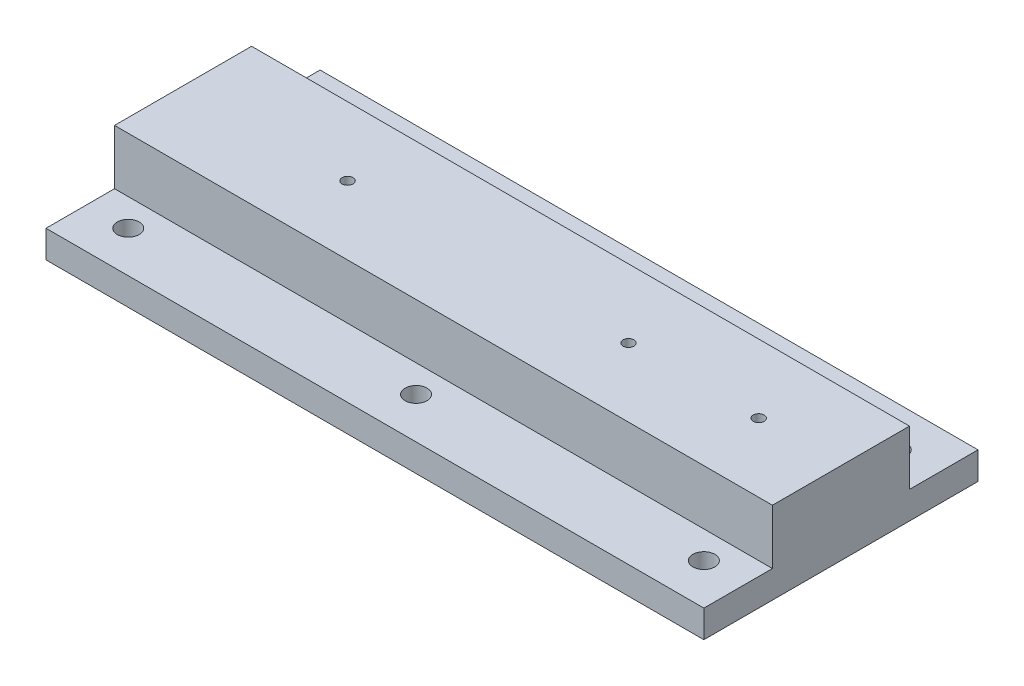
SolidWorks part; units mm, degrees
note: The reader was unsure of these and kept them because the rebuilt part matched: shared geometry of "Skizze7<2>".
ref_plane "Front Plane" through (0, 0, 0) normal (0, 0, 1) x (1, 0, 0)
ref_plane "Top Plane" through (0, 0, 0) normal (0, 1, 0) x (1, 0, 0)
ref_plane "Right Plane" through (0, 0, 0) normal (1, 0, 0) x (0, 0, -1)
sketch "Sketch2" plane through (0, 0, 0) normal (0, 1, 0) x (1, 0, 0)
  line L0 (-46.8981, 34.5466) -> (-46.8981, -15.4534)
  line L1 (-46.8981, -15.4534) -> (73.1019, -15.4534)
  line L2 (73.1019, -15.4534) -> (73.1019, 34.5466)
  line L3 (73.1019, 34.5466) -> (-46.8981, 34.5466)
  dimension "D1" = 120
  dimension "D2" = 50
extrude "Boss-Extrude1" add sketch "Sketch2" along normal blind 15
sketch "Sketch3" plane through (0, 0, 0) normal (0, 1, 0) x (1, 0, 0)
  line L0 (74.3548, 9.5466) -> (-56.2815, 9.5466) construction
  line L1 (63.1019, 9.5466) -> (63.1019, 17.0466)
  line L2 (63.1019, 17.0466) -> (3.1019, 17.0466)
  line L3 (3.1019, 17.0466) -> (3.1019, 19.5466)
  line L4 (3.1019, 19.5466) -> (-36.8981, 19.5466)
  line L5 (-36.8981, 19.5466) -> (-36.8981, 9.5466)
  line L6 (-36.8981, 9.5466) -> (63.1019, 9.5466)
  line L7 (73.1019, -15.4534) -> (73.1019, 34.5466) construction
  line L9 (-46.8981, -15.4534) -> (73.1019, -15.4534) construction
  dimension "D1" = 60
  dimension "D2" = 40
  dimension "D3" = 10
  dimension "D4" = 25
  dimension "D5" = 10
  dimension "D6" = 7.5
revolve "Cut-Revolve8" cut sketch "Sketch3" angle 360 about L0
ref_plane "Ebene1" through (63.1019, 0, 0) normal (-1, 0, 0) x (0, 0, 1)
sketch "Skizze2" plane through (63.1019, 0, 0) normal (-1, 0, 0) x (0, 0, 1)
  line L0 (-22.101, 0) -> (5.7524, 0) construction
  line L1 (-2.0466, 0) -> (-17.0466, 0) construction
  line L2 (-9.5466, -15.2765) -> (-9.5466, 13.7911) construction
  line L3 (-3.5466, 0) -> (-2.0466, 0)
  line L4 (-2.0466, 0) -> (-17.0466, 0) construction
  line L5 (-34.5466, 15) -> (-34.5466, 0) construction
  line L6 (15.4534, 15) -> (15.4534, 0) construction
  line L7 (-4.9281, 3.83) -> (-3.7734, 4.7875)
  arc A0 (-2.0466, 0) -> (-3.7734, 4.7875) centre (-9.5466, 0) ccw
  arc A1 (-3.5466, 0) -> (-4.9281, 3.83) centre (-9.5466, 0) ccw
  dimension "D1" = 1.5
  dimension "D2" = 7.5
  dimension "D3" = 1.5
  dimension "D4" = 3.83
ref_plane "Ebene2" through (28.1019, 0, 0) normal (-1, 0, 0) x (0, 0, 1)
extrude "Aufsatz-Linear austragen3" add sketch "Skizze2" along normal blind 47.5
ref_plane "Ebene3" through (0, 0, -9.5466) normal (0, 0, 1) x (1, 0, 0)
mirror "Spiegeln1" about plane through (0, 0, -9.5466) normal (0, 0, 1) of "Aufsatz-Linear austragen3"
sketch "Skizze7" plane through (63.1019, 0, 0) normal (-1, 0, 0) x (0, 0, 1)
  line L0 (-3.5466, 0) -> (-15.5466, 0) construction
  circle A0 centre (-9.5466, 0) radius 7.5
  arc A1 (-3.7734, 4.7875) -> (-15.3198, 4.7875) centre (-9.5466, 0) ccw construction
extrude "Schnitt-Linear austragen2" cut sketch "Skizze7" against normal blind 12.5 from surface at 35 starting at plane "Ebene2"
extrude "Schnitt-Linear austragen3" cut sketch "Skizze7<2>" along normal blind 10 contours A0
sketch "Skizze7<2>" plane through (63.1019, 0, 0) normal (-1, 0, 0) x (0, 0, 1) same geometry as "Skizze7"
sketch "Skizze8" plane through (0, 15, 0) normal (0, 1, 0) x (1, 0, 0)
  line L0 (91.3144, 9.5466) -> (-68.5218, 9.5466) construction
  line L1 (73.1019, 34.5466) -> (-46.8981, 34.5466) construction
  line L2 (-46.8981, -15.4534) -> (73.1019, -15.4534) construction
  line L3 (73.1019, -15.4534) -> (73.1019, 34.5466) construction
  line L4 (-46.8981, 34.5466) -> (-46.8981, -15.4534) construction
  circle A0 centre (58.1019, 9.5466) radius 1
  circle A1 centre (34.3519, 9.5466) radius 1
  circle A2 centre (-16.8981, 9.5466) radius 1
  dimension "D1" = 2
  dimension "D2" = 23.75
  dimension "D3" = 15
  dimension "D4" = 30
extrude "Schnitt-Linear austragen4" cut sketch "Skizze8" against normal up to next
sketch "Skizze9" plane through (-46.8981, 0, 0) normal (-1, 0, 0) x (0, 0, 1)
  line L0 (-34.5466, 5) -> (-22.0466, 5)
  line L1 (2.9534, 5) -> (2.9534, 15)
  line L2 (15.4534, 0) -> (-34.5466, 0) construction
  line L4 (2.9534, 5) -> (15.4534, 5)
  line L5 (15.4534, 15) -> (15.4534, 0) construction
  line L6 (-34.5466, 5) -> (-34.5466, 15)
  line L7 (-34.5466, 15) -> (15.4534, 15)
  line L8 (15.4534, 15) -> (15.4534, 5)
  line L9 (2.9534, 15) -> (-22.0466, 15)
  line L10 (-22.0466, 15) -> (-22.0466, 5)
  dimension "D1" = 5
  dimension "D2" = 12.5
  dimension "D3" = 12.5
extrude "Schnitt-Linear austragen5" cut sketch "Skizze9" against normal through all
sketch "Skizze10" plane through (0, 5, 0) normal (0, 1, 0) x (1, 0, 0)
  line L0 (73.1019, 34.5466) -> (73.1019, 22.0466) construction
  line L1 (73.1019, 34.5466) -> (-46.8981, 34.5466) construction
  circle A0 centre (65.6019, 27.0466) radius 2
  point P6 (0, 0)
  dimension "D1" = 4
  dimension "D2" = 7.5
  dimension "D3" = 7.5
extrude "Schnitt-Linear austragen7" cut sketch "Skizze10" against normal through all
sketch "Skizze11" plane through (0, 5, 0) normal (0, 1, 0) x (1, 0, 0)
  line L0 (80.5883, 9.5466) -> (-93.0916, 9.5466) construction
  line L1 (73.1019, 34.5466) -> (-46.8981, 34.5466) construction
  line L2 (73.1019, -15.4534) -> (-46.8981, -15.4534) construction
mirror "Spiegeln2" about plane through (0, 0, -9.5466) normal (0, 0, 1) of "Schnitt-Linear austragen7"
ref_plane "Ebene4" through (13.1019, 0, 0) normal (1, 0, 0) x (0, 0, -1)
mirror "Spiegeln3" about plane through (13.1019, 0, 0) normal (1, 0, 0) of "Schnitt-Linear austragen7", "Spiegeln2"
sketch "Skizze12" plane through (0, 5, 0) normal (0, 1, 0) x (1, 0, 0)
  line L0 (73.1019, -15.4534) -> (73.1019, 34.5466) construction
  line L1 (73.1019, 34.5466) -> (-46.8981, 34.5466) construction
  line L2 (73.1019, -15.4534) -> (-46.8981, -15.4534) construction
  circle A0 centre (13.1019, 27.0466) radius 2
  circle A1 centre (13.1019, -7.9534) radius 2
  circle A2 centre (65.6019, -7.9534) radius 2 construction
  dimension "D1" = 60
  dimension "D2" = 7.5
  dimension "D3" = 7.5
extrude "Schnitt-Linear austragen8" cut sketch "Skizze12" against normal blind 10
